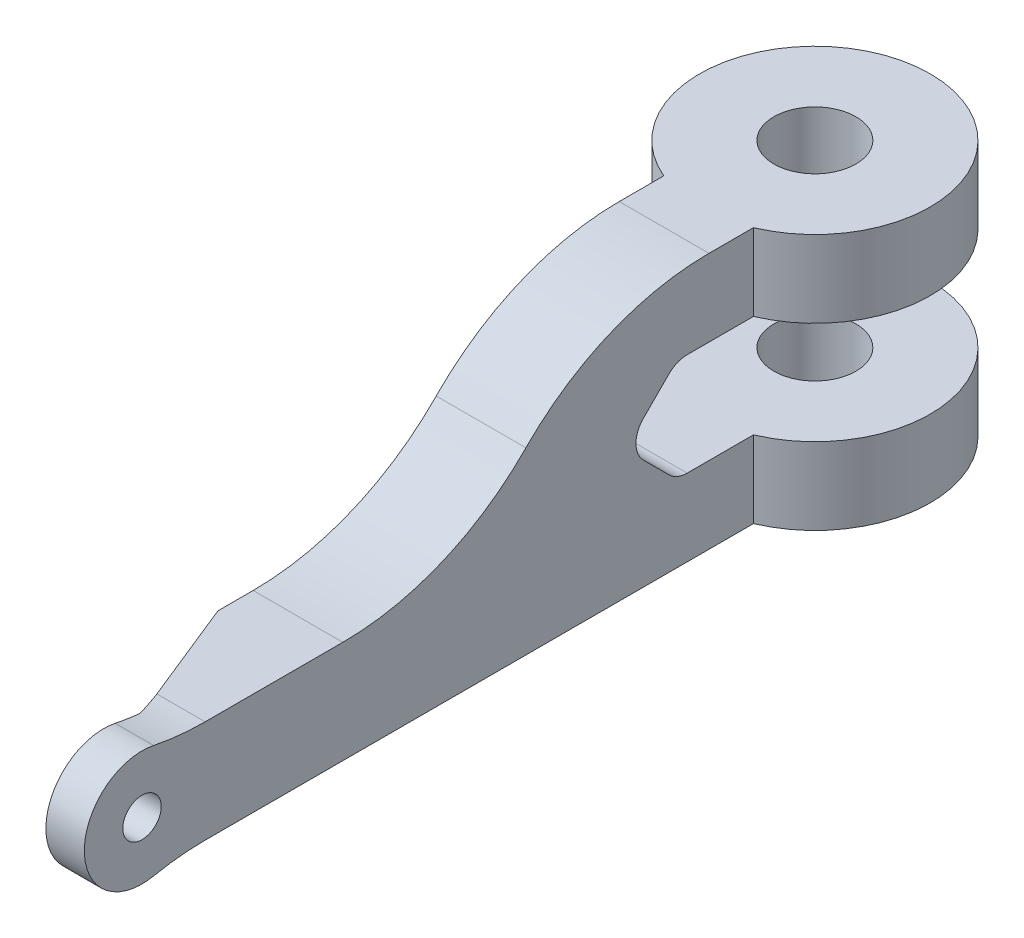
SolidWorks part; units mm, degrees
ref_plane "Front Plane" through (0, 0, 0) normal (0, 0, 1) x (1, 0, 0)
ref_plane "Top Plane" through (0, 0, 0) normal (0, 1, 0) x (1, 0, 0)
ref_plane "Right Plane" through (0, 0, 0) normal (1, 0, 0) x (0, 0, -1)
sketch "Sketch4" plane through (0, 0, 0) normal (0, 1, 0) x (1, 0, 0)
  circle A0 centre (0, 0) radius 1.6
  circle A1 centre (0, 0) radius 4.5
  dimension "D1" = 3.2
  dimension "D2" = 9
extrude "Boss-Extrude3" add sketch "Sketch4" along normal blind 3
sketch "Sketch5" plane through (0, 3, 0) normal (0, 1, 0) x (1, 0, 0)
  circle A0 centre (0, 0) radius 1.6
  circle A1 centre (0, 0) radius 4.5
extrude "Boss-Extrude4" add sketch "Sketch5" along normal blind 3 from offset 4 separate body
sketch "Sketch6" plane through (0, 10, 0) normal (0, 1, 0) x (1, 0, 0)
  line L1 (-1.75, 2) -> (1.75, 2)
  line L2 (-1.75, 2) -> (-1.75, -11)
  line L3 (-1.75, -11) -> (1.75, -11)
  line L4 (1.75, 2) -> (1.75, -11)
  line L5 (-1.75, 2) -> (1.75, -11) construction
  line L6 (-1.75, -11) -> (1.75, 2) construction
  circle A0 centre (0, 0) radius 4.5 construction
  circle A1 centre (0, 0) radius 4.5
  point P0 (0, -4.5)
  circle M3 centre (0, 0) radius 4.5
  dimension "D1" = 3.5
  dimension "D2" = 13
extrude "Boss-Extrude5" add sketch "Sketch6" against normal blind 10 contours L4 L2 L3 M3 region at (0, 10, 7.6911)
sketch "Sketch7" plane through (-1.75, 0, 0) normal (-1, 0, 0) x (0, 0, 1)
  line L2 (4.1458, 7) -> (4.1458, 3)
  line L3 (4.1458, 7) -> (7.1458, 7)
  line L4 (7.1458, 7) -> (9.1458, 5)
  line L5 (9.1458, 5) -> (7.1458, 3)
  line L6 (7.1458, 3) -> (4.1458, 3)
  point P3 (4.1458, 5)
  dimension "D1" = 0
  dimension "D2" = 0
  dimension "D3" = 3
extrude "Cut-Extrude1" cut sketch "Sketch7" against normal through all
sketch "Sketch8" plane through (0, 0, 11) normal (0, 0, 1) x (1, 0, 0)
  line L0 (-1.75, 0) -> (-1.75, 10) construction
  line L1 (-1.75, 0) -> (1.75, 0)
  line L2 (-1.75, 0) -> (-1.75, 4)
  line L3 (-1.75, 4) -> (1.75, 4)
  line L4 (1.75, 0) -> (1.75, 4)
  line L5 (1.75, 0) -> (1.75, 10) construction
  line L6 (-1.75, 0) -> (1.75, 0) construction
  dimension "D1" = 4
  dimension "D2" = 0
extrude "Boss-Extrude6" add sketch "Sketch8" along normal blind 17
sketch "Sketch9" plane through (1.75, 0, 0) normal (1, 0, 0) x (0, 0, -1)
  line L0 (-28, 0) -> (-28, 4) construction
  circle A0 centre (-28, 2) radius 0.75
  dimension "D1" = 1.5
extrude "Cut-Extrude2" cut sketch "Sketch9" against normal through all
sketch "Sketch10" plane through (1.75, 0, 0) normal (1, 0, 0) x (0, 0, -1)
  circle A0 centre (-28, 2) radius 2.25
  circle A1 centre (-28, 2) radius 0.75
  dimension "D1" = 1.5
  dimension "D2" = 4.5
extrude "Boss-Extrude7" add sketch "Sketch10" against normal blind 1.5
fillet "Fillet1" radius 10 3 edges at (0, 4, 11) (1, 4, 26.9692) (1, 0, 26.9692)
fillet "Fillet2" radius 10 1 edges at (0, 10, 11)
fillet "Fillet3" radius 1 3 edges at (0, 7, 7.1458) (0, 5, 9.1458) (0, 3, 7.1458)
sketch "Sketch11" plane through (0, 0, 0) normal (0, -1, 0) x (1, 0, 0)
  line L1 (-1.75, 28) -> (0.25, 28)
  line L2 (-1.75, 28) -> (-1.75, 25.5378)
  line L3 (-1.75, 25.5378) -> (0.25, 25.5378)
  line L4 (0.25, 28) -> (0.25, 25.5378)
extrude "Cut-Extrude3" cut sketch "Sketch11" against normal through all
chamfer "Chamfer2" distance 4 angle 22 1 edges at (-1.75, 2, 25.5378) first distance on face at (-1.75, 5, 10.1533)
chamfer "Chamfer3" distance 0.38 angle 70 1 edges at (0.25, 2, 25.5378) first distance on face at (0.0581, 2, 25.5378)
